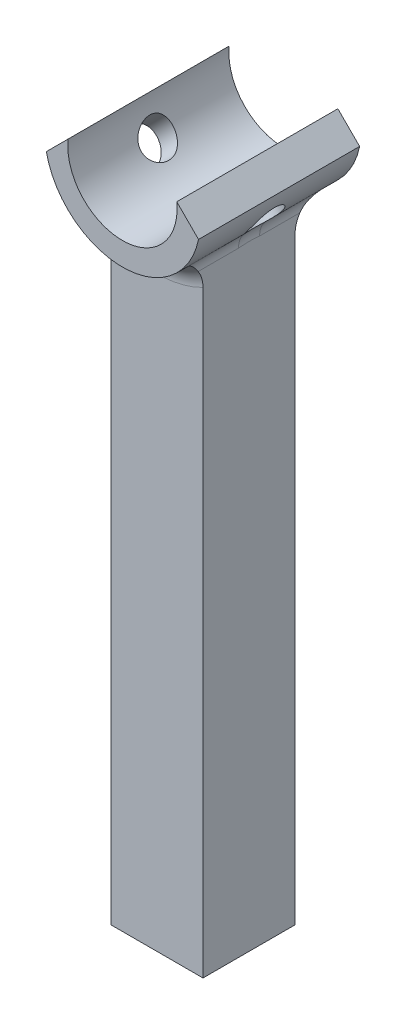
SolidWorks part; units mm, degrees
ref_plane "Front Plane" through (0, 0, 0) normal (0, 0, 1) x (1, 0, 0)
ref_plane "Top Plane" through (0, 0, 0) normal (0, 1, 0) x (1, 0, 0)
ref_plane "Right Plane" through (0, 0, 0) normal (1, 0, 0) x (0, 0, -1)
sketch "Sketch1" plane through (0, 0, 0) normal (0, 1, 0) x (1, 0, 0)
  line L1 (4, -15) -> (-4, -15)
  line L2 (4, -15) -> (4, -7)
  line L3 (4, -7) -> (-4, -7)
  line L4 (-4, -15) -> (-4, -7)
  point P4 (0, -7)
  dimension "D3" = 8
  dimension "D4" = 8
extrude "Boss-Extrude1" add sketch "Sketch1" against normal blind 55 contours L2 L3 L4 L1
sketch "Sketch2" plane through (0, 0, 0) normal (0, 0, 1) x (1, 0, 0)
  line L0 (-3.6183, 0) -> (3.4011, 0) construction
  line L1 (-8, 2) -> (8, 2) construction
  line L2 (-8, 2) -> (-4.4083, 5.5917)
  line L3 (8, 2) -> (3.6742, 6.3258)
  circle A0 centre (0, 4.75) radius 4.75
  circle A1 centre (0, 4.75) radius 6.75
  point P2 (-0.1086, 0)
  dimension "D1" = 0
  dimension "D3" = 2
  dimension "D4" = 45
  dimension "D5" = 45
  dimension "D6" = 8
  dimension "D7" = 8
  dimension "D2" = 2
extrude "Boss-Extrude2" add sketch "Sketch2" along normal blind 3 and the other way blind 11 from surface contours L2 A1 L3 A0 region at (-5.5591, 4.2274, 0) starting at face at (0, -27.5, 15)
ref_plane "Plane1" through (5, 5, 0) normal (0.7071, 0.7071, 0) x (0.7071, -0.7071, 0)
ref_plane "Plane2" through (-5.6066, -5.6066, 0) normal (-0.7071, -0.7071, 0) x (0.7071, -0.7071, 0)
sketch "Sketch4" plane through (-5.6066, -5.6066, 0) normal (-0.7071, -0.7071, 0) x (0.7071, -0.7071, 0)
  line L0 (-2.3425, 7) -> (-2.3425, 15) construction
  circle A0 centre (-4.3425, 11) radius 1.5
  point P4 (-2.3425, 11)
  point P5 (0, 0)
  dimension "D1" = 2
extrude "Cut-Extrude1" cut sketch "Sketch4" against normal through all
mirror "Mirror1" about plane through (0, 0, 0) normal (1, 0, 0) of "Cut-Extrude1"
fillet "Fillet1" radius 2 4 edges at (-4, -0.6871, 11) (0, -2, 7) (4, -0.6871, 11) (0, -2, 15)
